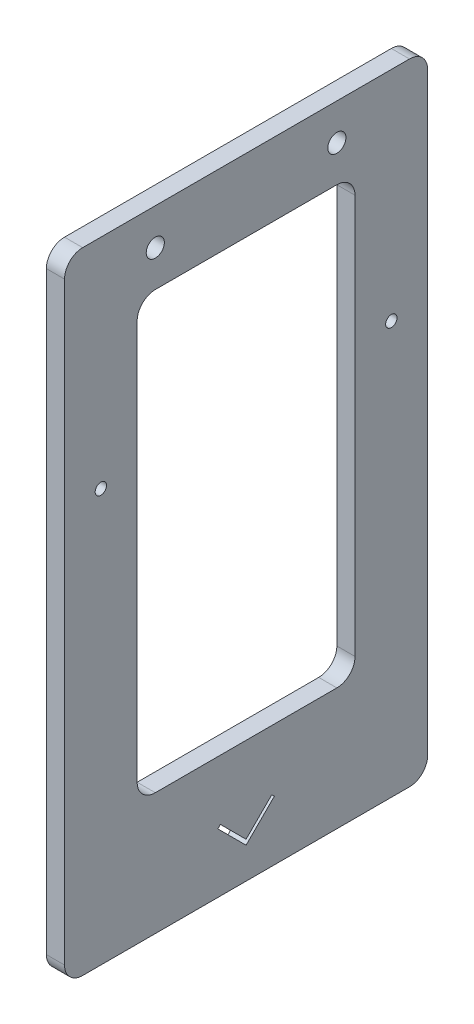
SolidWorks part; units mm, degrees
material "Balsa"
ref_plane "Front Plane" through (0, 0, 0) normal (0, 0, 1) x (1, 0, 0)
ref_plane "Top Plane" through (0, 0, 0) normal (0, 1, 0) x (1, 0, 0)
ref_plane "Right Plane" through (0, 0, 0) normal (1, 0, 0) x (0, 0, -1)
sketch "Sketch3" plane through (0, 0, 0) normal (1, 0, 0) x (0, 0, -1)
  line L0 (-31.75, -67.564) -> (31.75, -67.564)
  line L1 (-57.15, -110.236) -> (57.15, -110.236)
  line L2 (-63.5, -103.886) -> (-63.5, 103.886)
  line L3 (-57.15, 110.236) -> (57.15, 110.236)
  line L4 (63.5, -103.886) -> (63.5, 103.886)
  line L5 (-63.5, -110.236) -> (63.5, 110.236) construction
  line L6 (-63.5, 110.236) -> (63.5, -110.236) construction
  line L8 (-38.1, -61.214) -> (-38.1, 78.486)
  line L9 (-31.75, 84.836) -> (31.75, 84.836)
  line L11 (0, 0) -> (38.1, 84.836) construction
  line L12 (-38.1, 84.836) -> (0, 0) construction
  line L13 (38.1, -61.214) -> (38.1, 78.486)
  arc A0 (-57.15, -110.236) -> (-63.5, -103.886) centre (-57.15, -103.886) cw
  arc A1 (63.5, -103.886) -> (57.15, -110.236) centre (57.15, -103.886) cw
  arc A2 (63.5, 103.886) -> (57.15, 110.236) centre (57.15, 103.886) ccw
  arc A3 (-63.5, 103.886) -> (-57.15, 110.236) centre (-57.15, 103.886) cw
  arc A4 (31.75, -67.564) -> (38.1, -61.214) centre (31.75, -61.214) ccw
  arc A5 (-31.75, -67.564) -> (-38.1, -61.214) centre (-31.75, -61.214) cw
  arc A6 (31.75, 84.836) -> (38.1, 78.486) centre (31.75, 78.486) cw
  arc A7 (-38.1, 78.486) -> (-31.75, 84.836) centre (-31.75, 78.486) cw
  point P0 (0, 0)
  point P6 (0, 0)
  point P26 (38.1, -67.564)
  dimension "D7" = 6.35
  dimension "D8" = 6.35
  dimension "D1" = 220.472
  dimension "D2" = 127
  dimension "D3" = 76.2
  dimension "D4" = 152.4
  dimension "D5" = 25.4
  dimension "D6" = 25.4
extrude "Boss-Extrude2" add sketch "Sketch3" along normal blind 6.35
sketch "Sketch4" plane through (6.35, 0, 0) normal (1, 0, 0) x (0, 0, -1)
  line L0 (-57.15, -110.236) -> (57.15, -110.236) construction
  line L5 (0, -95.7399) -> (-8.9803, -86.7597) construction
  line L6 (-8.9803, -86.7597) -> (-9.8783, -87.6577) construction
  line L7 (0, -97.536) -> (-8.9803, -88.5557)
  line L8 (-9.8783, -87.6577) -> (0, -97.536) construction
  line L9 (0, -97.536) -> (9.8783, -87.6577) construction
  line L10 (9.8783, -87.6577) -> (8.9803, -86.7597) construction
  line L11 (8.9803, -86.7597) -> (0, -95.7399) construction
  line L12 (0, 3.4925) -> (0, -3.4925) construction
  line L13 (-8.9803, -88.5557) -> (-9.8783, -89.4538)
  line L14 (-9.8783, -89.4538) -> (0, -99.3321)
  line L15 (0, -97.536) -> (8.9803, -88.5557)
  line L16 (8.9803, -88.5557) -> (9.8783, -89.4538)
  line L17 (9.8783, -89.4538) -> (0, -99.3321)
  dimension "D1" = 12.7
  dimension "D2" = 12.7
  dimension "D3" = 1.27
  dimension "D4" = 12.7
  dimension "D5" = 1.27
extrude "Cut-Extrude1" cut sketch "Sketch4" against normal up to next
sketch "Sketch5" plane through (6.35, 0, 0) normal (1, 0, 0) x (0, 0, -1)
  line L0 (-31.75, 97.536) -> (31.75, 97.536) construction
  line L1 (31.75, 97.536) -> (63.5, 97.536) construction
  line L2 (63.5, -103.886) -> (63.5, 103.886) construction
  line L3 (-31.75, 97.536) -> (-63.5, 97.536) construction
  line L4 (-63.5, 103.886) -> (-63.5, -103.886) construction
  line L5 (57.15, 110.236) -> (-57.15, 110.236) construction
  circle A0 centre (-31.75, 97.536) radius 3.175
  circle A1 centre (31.75, 97.536) radius 3.175
  dimension "D1" = 6.35
  dimension "D2" = 63.5
  dimension "D3" = 12.7
extrude "Cut-Extrude2" cut sketch "Sketch5" against normal through all both and the other way through all
sketch "Sketch6" plane through (6.35, 0, 0) normal (1, 0, 0) x (0, 0, -1)
  line L0 (0, 3.4925) -> (0, -3.4925) construction
  line L1 (57.15, 110.236) -> (-57.15, 110.236) construction
  circle A0 centre (-50.8, 34.036) radius 1.9844
  circle A1 centre (50.8, 34.036) radius 1.9844
  dimension "D1" = 3.9688
  dimension "D2" = 50.8
  dimension "D3" = 76.2
extrude "Cut-Extrude3" cut sketch "Sketch6" against normal through all
